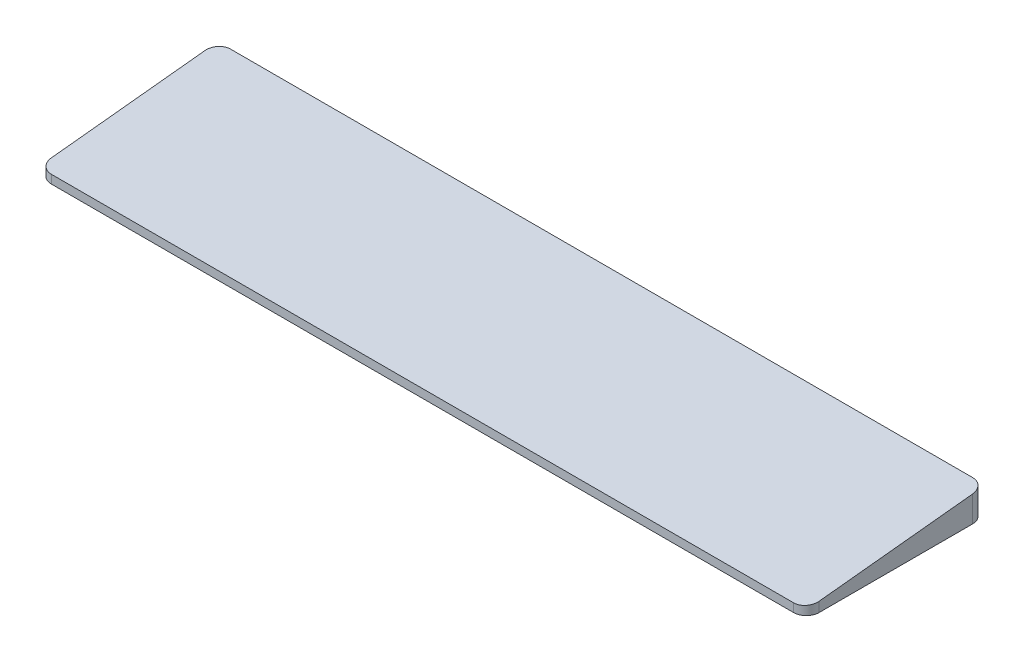
SolidWorks part; units mm, degrees
material "Brass"
ref_plane "Front Plane" through (0, 0, 0) normal (0, 0, 1) x (1, 0, 0)
ref_plane "Top Plane" through (0, 0, 0) normal (0, 1, 0) x (1, 0, 0)
ref_plane "Right Plane" through (0, 0, 0) normal (1, 0, 0) x (0, 0, -1)
sketch "Sketch1" plane through (0, 0, 0) normal (0, 1, 0) x (1, 0, 0)
  line L1 (0, 0) -> (300, 0)
  line L2 (0, 0) -> (0, 70)
  line L3 (0, 70) -> (300, 70)
  line L4 (300, 0) -> (300, 70)
  dimension "D1" = 300
  dimension "D2" = 70
ref_plane "Plane1" through (0, 0, 0) normal (0, 0.9945, 0.1045) x (1, 0, 0)
ref_plane "Plane2" through (0, 3.2819, 0.3449) normal (0, 0.9945, 0.1045) x (1, 0, 0)
extrude "Boss-Extrude1" add sketch "Sketch1" along normal up to surface (3.3182 mm away) contours L3 L4 L1 L2 up to plane "Plane2"
fillet "Fillet1" radius 5 4 edges at (300, 5.3377, -70) (300, 1.6591, 0) (0, 1.6591, 0) (0, 5.3377, -70)
sketch "Sketch2" plane through (0, 0, 0) normal (0, -1, 0) x (1, 0, 0)
  line L0 (153, -32) -> (151, -32) construction
  line L1 (153, -40) -> (151, -40)
  line L2 (153, -40) -> (153, -24)
  line L3 (153, -24) -> (151, -24)
  line L4 (151, -40) -> (151, -24)
  line L5 (157.5, -32.5) -> (155.5, -32.5)
  line L6 (157.5, -32.5) -> (157.5, -20)
  line L7 (157.5, -20) -> (155.5, -20)
  line L8 (155.5, -32.5) -> (155.5, -20)
  line L9 (148.2, -32.5) -> (146.2, -32.5)
  line L10 (148.2, -32.5) -> (148.2, -24.5)
  line L11 (148.2, -24.5) -> (146.2, -24.5)
  line L12 (146.2, -32.5) -> (146.2, -24.5)
  line L13 (144.7, -32.5) -> (142.7, -32.5)
  line L14 (144.7, -32.5) -> (144.7, -24.5)
  line L15 (144.7, -24.5) -> (142.7, -24.5)
  line L16 (142.7, -32.5) -> (142.7, -24.5)
  line L17 (141.2, -32.5) -> (139.2, -32.5)
  line L18 (141.2, -32.5) -> (141.2, -24.5)
  line L19 (141.2, -24.5) -> (139.2, -24.5)
  line L20 (139.2, -32.5) -> (139.2, -24.5)
  line L21 (157.5, -32.5) -> (142.7, -32.5) construction
  line L22 (149, -36) -> (153, -36)
  line L23 (149, -34) -> (153, -34)
  line L24 (161, -24.5) -> (159, -24.5)
  line L25 (161, -24.5) -> (161, -20)
  line L26 (161, -20) -> (159, -20)
  line L27 (159, -24.5) -> (159, -20)
  line L28 (300, -5) -> (300, -65) construction
  line L29 (5, 0) -> (295, 0) construction
  circle A0 centre (156.5, -35) radius 1
  circle A1 centre (149, -35) radius 1
  circle A2 centre (152, -39) radius 1
  circle A3 centre (152, -25) radius 1
  circle A4 centre (156.5, -31.5) radius 1
  circle A5 centre (156.5, -21) radius 1
  circle A6 centre (160, -23.5) radius 1
  circle A7 centre (160, -21) radius 1
  circle A8 centre (147.2, -31.5) radius 1
  circle A9 centre (147.2, -25.5) radius 1
  circle A10 centre (143.7, -31.5) radius 1
  circle A11 centre (143.7, -25.5) radius 1
  circle A12 centre (140.2, -31.5) radius 1
  circle A13 centre (140.2, -25.5) radius 1
  point P28 (156.5, -32.5)
  point P38 (152, -40)
  dimension "D10" = 2
  dimension "D12" = 2
  dimension "D1" = 16
  dimension "D2" = 2
  dimension "D3" = 2.5
  dimension "D4" = 2.8
  dimension "D5" = 1.5
  dimension "D6" = 1.5
  dimension "D7" = 8
  dimension "D8" = 0.5
  dimension "D9" = 2.5
  dimension "D11" = 12.5
  dimension "D13" = 0
  dimension "D14" = 1.5
  dimension "D15" = 4.5
  dimension "D16" = 2
  dimension "D17" = 3
  dimension "D18" = 11
  dimension "D19" = 147
  dimension "D20" = 20
extrude "Cut-Extrude3" cut sketch "Sketch2" against normal blind 2 contours A7 L27 A6 L25 | A6 | A7 | A5 L8 A4 L6 | A0 | A4 | A3 L4 L23 L2 | L23 L4 L22 L2 | A2 L2 L22 L4 | A2 | A3 | A1 | A1 L22 L4 L23 | A8 | A9 L12 A8 L10 | A9 | A11 L16 A10 L14 | A10 | A11 | A13 | A13 L20 A12 L18 | A12 | A5 region at (152, 0, -39) region at (152, 0, -37.1185) region at (152, 0, -35) region at (150.3722, 0, -35) region at (152, 0, -29.8897) region at (149, 0, -35) region at (152, 0, -25) region at (156.5, 0, -31.5) region at (156.5, 0, -26.25) region at (147.2, 0, -31.5) region at (147.2, 0, -28.5) region at (147.2, 0, -25.5) region at (143.7, 0, -31.5) region at (143.7, 0, -28.5) region at (143.7, 0, -25.5) region at (140.2, 0, -31.5) region at (140.2, 0, -28.5) region at (140.2, 0, -25.5) region at (160, 0, -23.5) region at (160, 0, -22.25) region at (160, 0, -21) region at (156.5, 0, -35)
